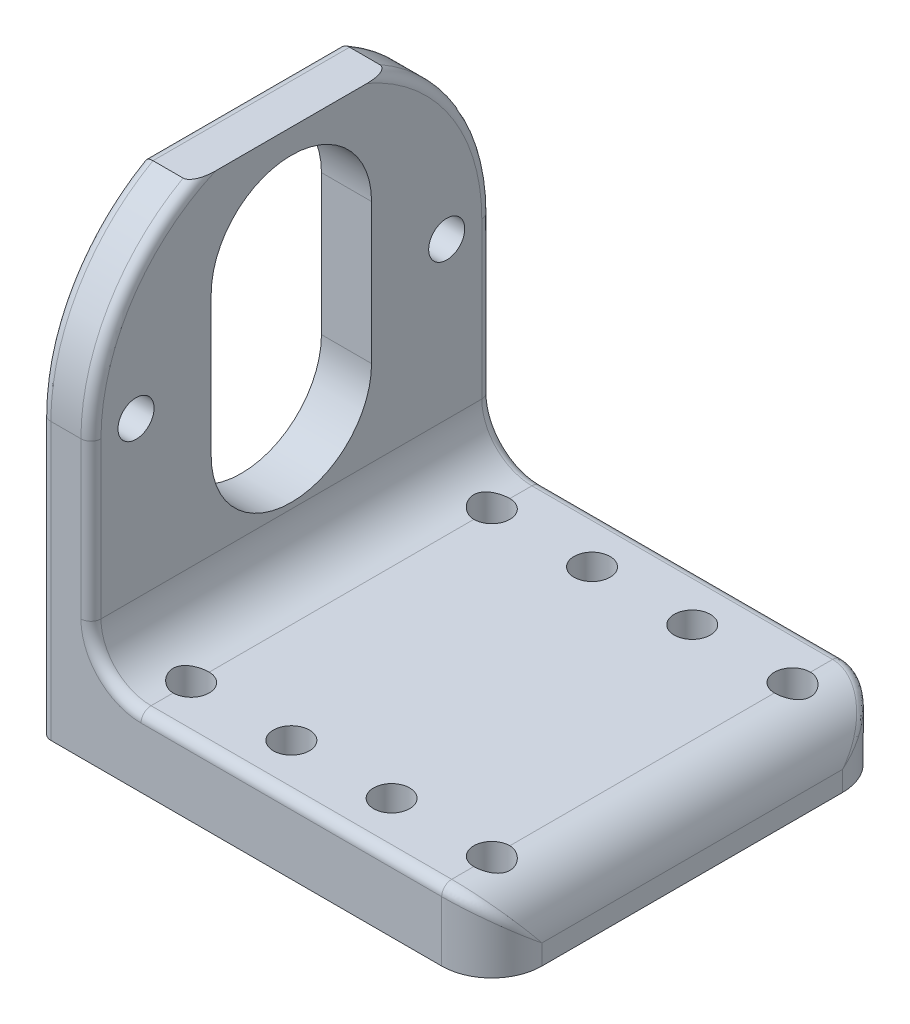
SolidWorks part; units mm, degrees
ref_plane "Front Plane" through (0, 0, 0) normal (0, 0, 1) x (1, 0, 0)
ref_plane "Top Plane" through (0, 0, 0) normal (0, 1, 0) x (1, 0, 0)
ref_plane "Right Plane" through (0, 0, 0) normal (1, 0, 0) x (0, 0, -1)
sketch "Sketch1" plane through (0, 0, 0) normal (0, 1, 0) x (1, 0, 0)
  line L0 (20, 15) -> (-20, 15) construction
  line L1 (-20, -20) -> (20, -20)
  line L2 (-20, -20) -> (-20, 20)
  line L3 (-20, 20) -> (20, 20)
  line L4 (20, -20) -> (20, 20)
  line L5 (-20, -20) -> (20, 20) construction
  line L6 (-20, 20) -> (20, -20) construction
  line L7 (-20, 20) -> (-25, 20)
  line L8 (-20, 20) -> (-20, -20)
  line L9 (-20, -20) -> (-25, -20)
  line L10 (-25, 20) -> (-25, -20)
  line L11 (-20, 20) -> (-25, -20) construction
  line L12 (-20, -20) -> (-25, 20) construction
  line L13 (-1000, 0) -> (49000, 0) construction
  line L14 (15, 15) -> (5, 15) construction
  circle A0 centre (15, 15) radius 1.8
  circle A1 centre (5, 15) radius 1.8
  circle A2 centre (-5, 15) radius 1.8
  circle A3 centre (-15, 15) radius 1.8
  circle A4 centre (15, -15) radius 1.8
  circle A5 centre (5, -15) radius 1.8
  circle A6 centre (-5, -15) radius 1.8
  circle A7 centre (-15, -15) radius 1.8
  point P0 (0, 0)
  point P8 (-22.5, 0)
  dimension "D4" = 3.6
  dimension "D5" = 5
  dimension "D1" = 40
  dimension "D2" = 5
  dimension "D3" = 5
  dimension "D7" = 10
  dimension "D6" = 4
extrude "Boss-Extrude1" add sketch "Sketch1" along normal blind 7 contours L1 L4 L3 L2 A6 A4 A3 A2 A1 A0 A5 A7 region at (0, 0, 0)
extrude "Boss-Extrude2" add sketch "Sketch1<3>" along normal blind 45 contours L7 L10 L9 L2 region at (-22.5, 0, 0)
sketch "Sketch1<3>" plane through (0, 0, 0) normal (0, 1, 0) x (1, 0, 0) same geometry as "Sketch1"
sketch "Sketch2" plane through (-25, 0, 0) normal (-1, 0, 0) x (0, 0, 1)
  line L0 (-1025.6474, 27.569) -> (48974.3526, 27.569) construction
  line L2 (0, 20.569) -> (0, 34.569) construction
  line L3 (-8, 20.569) -> (-8, 34.569)
  line L4 (8, 20.569) -> (8, 34.569)
  line L5 (0, -55) -> (0, 55) construction
  line L6 (-20, 27.569) -> (-20, 0)
  line L7 (-20, 0) -> (20, 0)
  line L8 (20, 0) -> (20, 27.569)
  line L12 (-20, 0) -> (20, 0) construction
  arc A0 (20, 27.569) -> (-20, 27.569) centre (0, 27.569) ccw
  arc A1 (-8, 20.569) -> (8, 20.569) centre (0, 20.569) ccw
  arc A2 (8, 34.569) -> (-8, 34.569) centre (0, 34.569) ccw
  circle A3 centre (-15.5, 27.569) radius 1.8
  circle A4 centre (15.5, 27.569) radius 1.8
  point P8 (0, 27.569)
  dimension "D2" = 40
  dimension "D3" = 16
  dimension "D4" = 14
  dimension "D5" = 3.6
  dimension "D6" = 31
  dimension "D1" = 20.569
extrude "Cut-Extrude1" cut sketch "Sketch2" against normal through all contours A3 | L4 A2 L3 A1 | A4 region at (-25, 27.569, 0) region at (-25, 27.569, -15.5) region at (-25, 27.569, 15.5)
extrude "Cut-Extrude2" cut sketch "Sketch2<4>" against normal through all flip side to cut
sketch "Sketch2<4>" plane through (-25, 0, 0) normal (-1, 0, 0) x (0, 0, 1) same geometry as "Sketch2"
fillet "Fillet1" radius 5 1 edges at (-20, 7, 0)
fillet "Fillet2" radius 5 3 edges at (20, 3.5, -20) (20, 3.5, 20) (20, 7, 0)
fillet "Fillet3" radius 1 15 edges at (-20, 19.7845, -20) (-18.5355, 8.4645, -20) (18.5355, 5.5355, -18.5355) (-20, 37.6655, 17.2645) (-20, 19.7845, 20) (-18.5355, 8.4645, 20) (18.5355, 5.5355, 18.5355) (0, 7, -20) (0, 7, 20) (-25, 37.6655, -17.2645) (-25, 45, 0) (-25, 37.6655, 17.2645) (-25, 13.7845, -20) (-25, 13.7845, 20) (-20, 37.6655, -17.2645)
sketch "Sketch4" plane through (0, 0, 0) normal (0, 0, 1) x (1, 0, 0)
  line L0 (-1016.9614, 27.569) -> (48983.0386, 27.569) construction
  line L2 (-21, 27.569) -> (-24, 27.569) construction
  line L3 (-1025, 34.569) -> (48975, 34.569) construction
  line L5 (-1018.0144, 20.569) -> (48981.9856, 20.569) construction
  dimension "D1" = 7
  dimension "D2" = 7
ref_axis "Axis1" through (-1018.0144, 20.569, 0) along (1, 0, 0)
ref_axis "Axis2" through (-1025, 34.569, 0) along (1, 0, 0)
